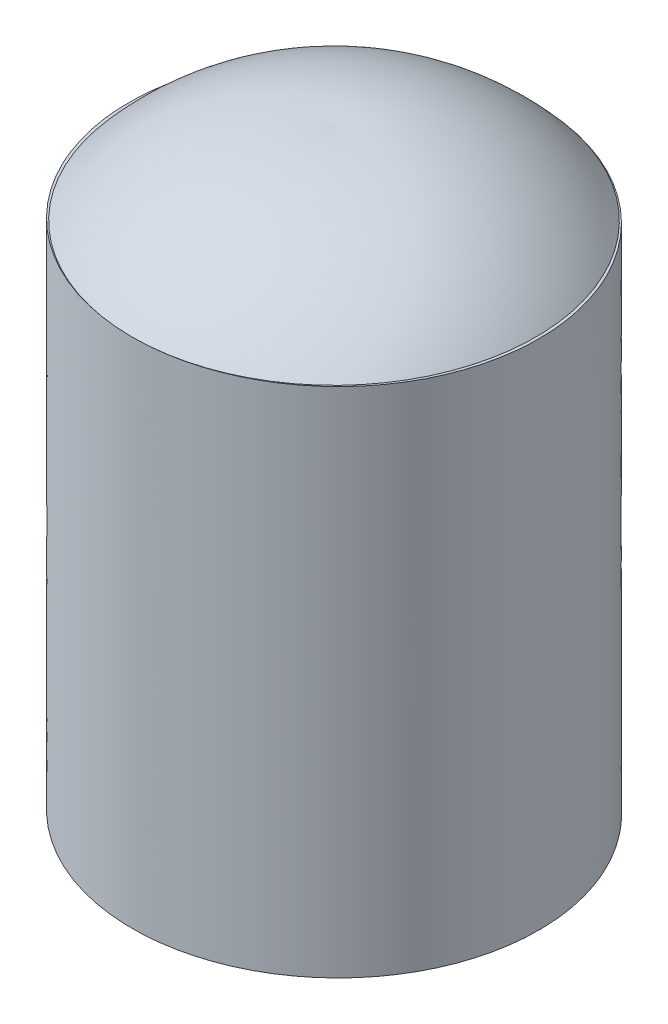
SolidWorks part; units mm, degrees
material "PF"
ref_plane "Front Plane" through (0, 0, 0) normal (0, 0, 1) x (1, 0, 0)
ref_plane "Top Plane" through (0, 0, 0) normal (0, 1, 0) x (1, 0, 0)
ref_plane "Right Plane" through (0, 0, 0) normal (1, 0, 0) x (0, 0, -1)
sketch "Sketch1" plane through (0, 0, 0) normal (0, 1, 0) x (1, 0, 0)
  ellipse E0 centre (0, 0) end of major axis (-8, 0) minor radius 7.72
sketch "Sketch2" plane through (0, 0, 0) normal (0, 1, 0) x (1, 0, 0)
  ellipse E0 centre (0, 0) end of major axis (-9.6881, 0) minor radius 9.5469
ref_plane "Plane1" through (0, -24.231, 0) normal (0, 1, 0) x (1, 0, 0)
sketch "Sketch5" plane through (0, -24.231, 0) normal (0, 1, 0) x (1, 0, 0)
  ellipse E0 centre (0, 0) end of major axis (-9.6881, 0) minor radius 9.5469
loft "Loft2" add profiles "Sketch2", "Sketch5" connector at (-9.6881, 0, 0.006) connector at (-9.681, -24.231, 0.3658)
extrude "Cut-Extrude1" cut sketch "Sketch1" against normal blind 61 contours E0
ref_plane "Plane2" through (0, -10, 0) normal (0, 1, 0) x (1, 0, 0)
sketch "Sketch7" plane through (0, 0, 0) normal (1, 0, 0) x (0, 0, -1)
  line L0 (0, 3.9545) -> (0, 0)
  line L1 (9.5469, 0) -> (0, 0)
  arc A0 (9.5469, 0) -> (0, 3.9545) centre (0.808, -7.5963) ccw
sketch "Sketch8" plane through (0, 0, 0) normal (1, 0, 0) x (0, 0, -1)
  line L0 (0, 0) -> (0, -9.3223)
revolve "Revolve1" add sketch "Sketch7" angle 360 about L0
